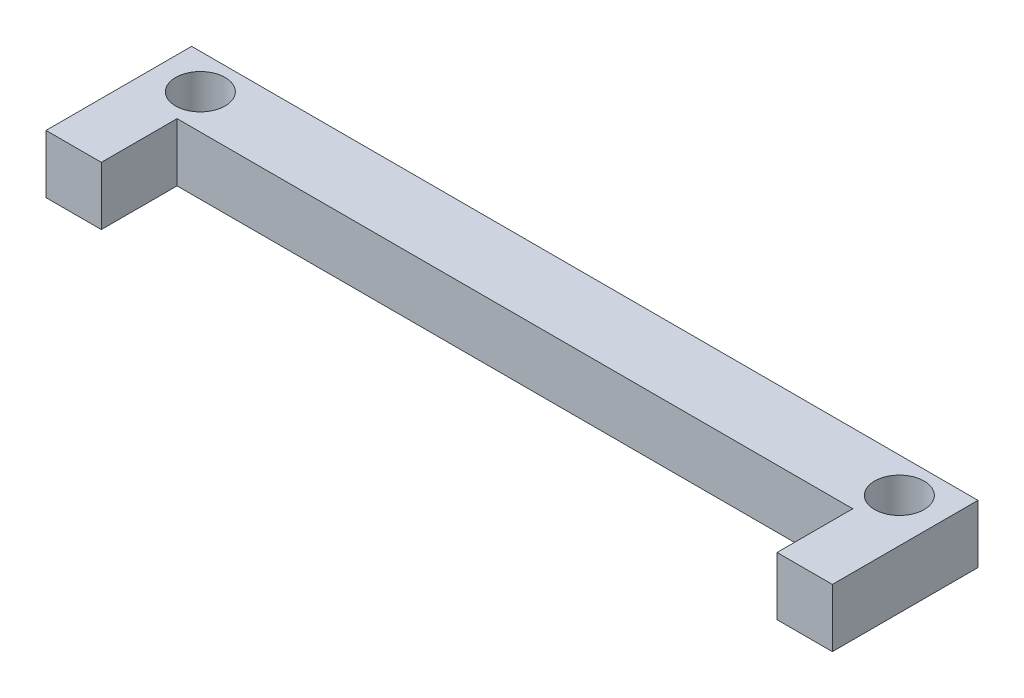
SolidWorks part; units mm, degrees
ref_plane "Front Plane" through (0, 0, 0) normal (0, 0, 1) x (1, 0, 0)
ref_plane "Top Plane" through (0, 0, 0) normal (0, 1, 0) x (1, 0, 0)
ref_plane "Right Plane" through (0, 0, 0) normal (1, 0, 0) x (0, 0, -1)
sketch "Sketch1" plane through (0, 0, 0) normal (0, 1, 0) x (1, 0, 0)
  line L0 (-55, 0) -> (55, 0) construction
  line L1 (-67.5, 12) -> (67.5, 12)
  line L3 (-58, 0) -> (58, 0)
  line L4 (67.5, 12) -> (67.5, 0)
  line L8 (-67.5, -13) -> (-58, -13)
  line L9 (-58, -13) -> (-58, 0)
  line L10 (0, -55) -> (0, 55) construction
  line L11 (67.5, -13) -> (58, -13)
  line L12 (58, -13) -> (58, 0)
  line L13 (67.5, 0) -> (67.5, -13)
  line L14 (-60, 6) -> (-60, 0) construction
  line L15 (-60, 6) -> (-67.5, 6) construction
  line L16 (-60, 6) -> (-60, 12) construction
  line L19 (-67.5, 12) -> (-67.5, -13)
  circle A0 centre (-60, 6) radius 4.25
  circle A1 centre (60, 6) radius 4.25
  point P2 (0, 0)
  point P6 (0, 0)
  dimension "D2" = 8.5
  dimension "D1" = 135
  dimension "D3" = 116
  dimension "D4" = 25
  dimension "D5" = 120
  dimension "D6" = 6
  dimension "D7" = 7.5
extrude "Boss-Extrude1" add sketch "Sketch1" along normal blind 10
